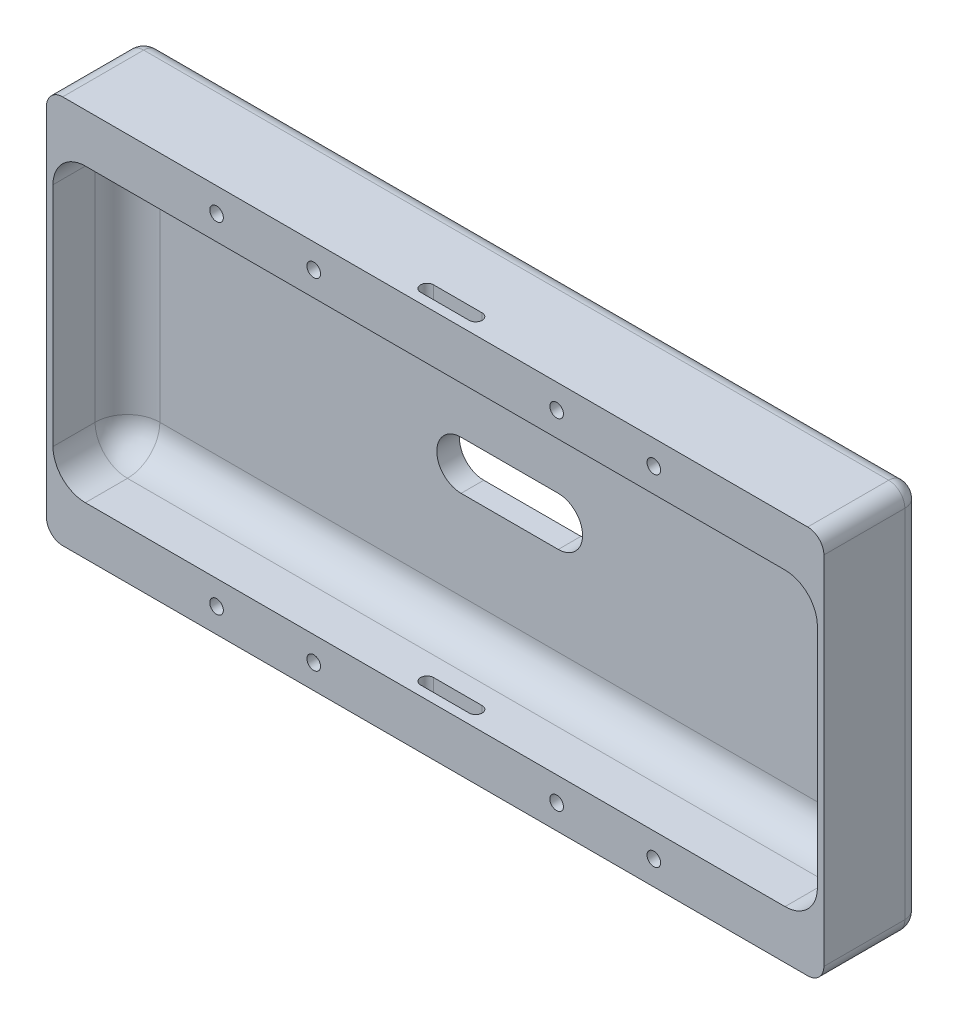
SolidWorks part; units mm, degrees
ref_plane "Front Plane" through (0, 0, 0) normal (0, 0, 1) x (1, 0, 0)
ref_plane "Top Plane" through (0, 0, 0) normal (0, 1, 0) x (1, 0, 0)
ref_plane "Right Plane" through (0, 0, 0) normal (1, 0, 0) x (0, 0, -1)
sketch "Sketch1" plane through (0, 0, 0) normal (0, 0, 1) x (1, 0, 0)
  line L1 (120, 60) -> (-120, 60)
  line L2 (120, 60) -> (120, -60)
  line L3 (120, -60) -> (-120, -60)
  line L4 (-120, 60) -> (-120, -60)
  line L5 (120, 60) -> (-120, -60) construction
  line L6 (120, -60) -> (-120, 60) construction
  point P0 (0, 0)
  dimension "D1" = 240
  dimension "D2" = 120
extrude "Boss-Extrude1" add sketch "Sketch1" against normal blind 30
sketch "Sketch2" plane through (-120, 0, 0) normal (-1, 0, 0) x (0, 0, 1)
  line L12 (0, 45) -> (-23, 45)
  line L13 (0, 60) -> (0, -60) construction
  line L14 (-23, 45) -> (-23, -45)
  line L15 (-23, -45) -> (0, -45)
  line L16 (0, -45) -> (0, 45)
  line L17 (-30, 60) -> (-30, -60) construction
  line L18 (-30, 60) -> (0, 60) construction
  line L19 (-30, -60) -> (0, -60) construction
  point P13 (0, 0)
  point P17 (0, 0)
  point P18 (0, 0)
  dimension "D1" = 7
  dimension "D2" = 15
  dimension "D3" = 15
extrude "Cut-Extrude1" cut sketch "Sketch2" against normal blind 241
fillet "Fillet1" [suppressed] radius 5
sketch "Sketch4" plane through (0, 0, -30) normal (0, 0, -1) x (-1, 0, 0)
  line L0 (15, 0) -> (-15, 0) construction
  line L1 (15, -7.5) -> (-15, -7.5)
  line L2 (15, 7.5) -> (-15, 7.5)
  arc A0 (15, -7.5) -> (15, 7.5) centre (15, 0) ccw
  arc A1 (-15, 7.5) -> (-15, -7.5) centre (-15, 0) ccw
  point P2 (0, 0)
  dimension "D2" = 7.5
  dimension "D1" = 30
extrude "Cut-Extrude2" cut sketch "Sketch4" against normal up to next
sketch "Sketch6" plane through (0, 0, 0) normal (0, 0, 1) x (1, 0, 0)
  line L1 (-87.5, 52.5) -> (87.5, 52.5) construction
  line L2 (-87.5, 52.5) -> (-87.5, -52.5) construction
  line L3 (-87.5, -52.5) -> (87.5, -52.5) construction
  line L4 (87.5, 52.5) -> (87.5, -52.5) construction
  line L5 (-87.5, 52.5) -> (87.5, -52.5) construction
  line L6 (-87.5, -52.5) -> (87.5, 52.5) construction
  line L9 (0, 52.5) -> (0, -52.5) construction
  line L10 (-87.5, 0) -> (87.5, 0) construction
  circle A8 centre (67.5, -52.5) radius 2.1
  circle A9 centre (37.5, -52.5) radius 2.1
  circle A10 centre (-37.5, -52.5) radius 2.1
  circle A11 centre (-67.5, -52.5) radius 2.1
  circle A12 centre (-67.5, 52.5) radius 2.1
  circle A13 centre (-37.5, 52.5) radius 2.1
  circle A14 centre (67.5, 52.5) radius 2.1
  circle A15 centre (37.5, 52.5) radius 2.1
  point P0 (0, 0)
  dimension "D5" = 4.2
  dimension "D1" = 105
  dimension "D2" = 175
  dimension "D3" = 20
  dimension "D4" = 30
extrude "Cut-Extrude3" cut sketch "Sketch6" against normal up to next
sketch "Sketch7" plane through (0, 0, -30) normal (0, 0, -1) x (-1, 0, 0)
  circle A0 centre (67.5, -52.5) radius 4
  circle A1 centre (37.5, -52.5) radius 4
  circle A2 centre (-37.5, -52.5) radius 4
  circle A3 centre (-67.5, -52.5) radius 4
  circle A4 centre (67.5, 52.5) radius 4
  circle A5 centre (37.5, 52.5) radius 4
  circle A6 centre (-37.5, 52.5) radius 4
  circle A7 centre (-67.5, 52.5) radius 4
  dimension "D1" = 8
extrude "Cut-Extrude4" cut sketch "Sketch7" against normal blind 4
sketch "Sketch8" plane through (0, 45, 0) normal (0, -1, 0) x (1, 0, 0)
  line L0 (-120, -23) -> (-120, 0)
  line L1 (-120, 0) -> (-118, 0)
  line L2 (120, 0) -> (-120, 0) construction
  line L3 (-118, 0) -> (-118, -23)
  line L4 (120, -23) -> (-120, -23) construction
  line L5 (-118, -23) -> (-120, -23)
  line L6 (120, -23) -> (118, -23)
  line L7 (118, -23) -> (118, 0)
  line L8 (118, 0) -> (120, 0)
  line L9 (120, 0) -> (120, -23)
  dimension "D1" = 2
  dimension "D2" = 2
extrude "Boss-Extrude2" add sketch "Sketch8" along normal blind 90
fillet "Fillet2" radius 5 8 edges at (120, 60, -15) (120, -60, -15) (-120, -60, -15) (-120, 60, -15) (120, 0, -30) (0, -60, -30) (-120, 0, -30) (0, 60, -30)
fillet "Fillet3" radius 10 8 edges at (-118, 0, -23) (118, 0, -23) (118, 45, -11.5) (118, -45, -11.5) (-118, -45, -11.5) (-118, 45, -11.5) (0, 45, -23) (0, -45, -23)
sketch "Sketch9" plane through (0, -60, 0) normal (0, -1, 0) x (1, 0, 0)
  line L0 (-7.5, -5) -> (7.5, -5) construction
  line L1 (-7.5, -3) -> (7.5, -3)
  line L2 (-7.5, -7) -> (7.5, -7)
  line L3 (0, -25) -> (0, -1) construction
  line L4 (-115, -25) -> (115, -25) construction
  line L5 (-115, -1) -> (115, -1) construction
  arc A0 (-7.5, -3) -> (-7.5, -7) centre (-7.5, -5) ccw
  arc A1 (7.5, -7) -> (7.5, -3) centre (7.5, -5) ccw
  point P2 (0, -5)
  point P7 (0, 0)
  dimension "D2" = 2
  dimension "D1" = 15
  dimension "D3" = 4
extrude "Cut-Extrude5" cut sketch "Sketch9" against normal blind 125
